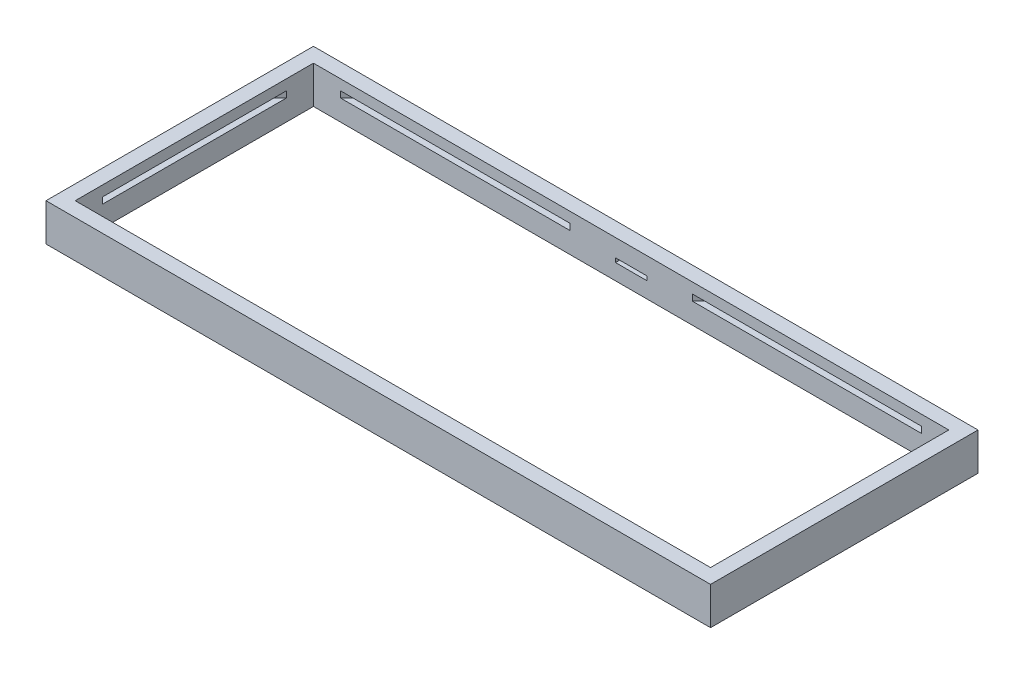
SolidWorks part; units mm, degrees
ref_plane "Front Plane" through (0, 0, 0) normal (0, 0, 1) x (1, 0, 0)
ref_plane "Top Plane" through (0, 0, 0) normal (0, 1, 0) x (1, 0, 0)
ref_plane "Right Plane" through (0, 0, 0) normal (1, 0, 0) x (0, 0, -1)
sketch "Sketch1" plane through (0, 0, 0) normal (0, 1, 0) x (1, 0, 0)
  line L0 (7, -7) -> (311.8, -7)
  line L1 (0, 0) -> (318.8, 0)
  line L2 (0, 0) -> (0, -128.3)
  line L3 (0, -128.3) -> (318.8, -128.3)
  line L4 (318.8, 0) -> (318.8, -128.3)
  line L5 (311.8, -7) -> (311.8, -121.3)
  line L6 (7, -121.3) -> (311.8, -121.3)
  line L7 (7, -7) -> (7, -121.3)
  dimension "D1" = 318.8
  dimension "D2" = 128.3
  dimension "D3" = 7
extrude "Boss-Extrude1" add sketch "Sketch1" along normal blind 8
sketch "Sketch2" plane through (0, 0, 0) normal (0, -1, 0) x (1, 0, 0)
  line L0 (7, 121.3) -> (311.8, 121.3) construction
  line L1 (20, 121.3) -> (130, 121.3)
  line L2 (20, 121.3) -> (20, 124.3)
  line L3 (20, 124.3) -> (130, 124.3)
  line L4 (130, 121.3) -> (130, 124.3)
  line L5 (159.4, 128.3) -> (159.4, 0)
  line L6 (0, 128.3) -> (318.8, 128.3) construction
  line L7 (318.8, 0) -> (0, 0) construction
  line L8 (0, 0) -> (0, 128.3) construction
  line L9 (0, 64.15) -> (318.8, 64.15)
  line L10 (318.8, 128.3) -> (318.8, 0) construction
  line L11 (20, 4) -> (130, 4)
  line L12 (130, 7) -> (130, 4)
  line L13 (20, 7) -> (130, 7)
  line L14 (20, 7) -> (20, 4)
  line L15 (7, 7) -> (7, 121.3) construction
  line L16 (7, 108.3) -> (4, 108.3)
  line L17 (7, 108.3) -> (7, 20)
  line L18 (7, 20) -> (4, 20)
  line L19 (4, 108.3) -> (4, 20)
  line L20 (298.8, 7) -> (298.8, 4)
  line L21 (298.8, 7) -> (188.8, 7)
  line L22 (188.8, 7) -> (188.8, 4)
  line L23 (298.8, 4) -> (188.8, 4)
  line L24 (311.8, 20) -> (314.8, 20)
  line L25 (314.8, 108.3) -> (314.8, 20)
  line L26 (311.8, 108.3) -> (314.8, 108.3)
  line L27 (311.8, 108.3) -> (311.8, 20)
  line L28 (298.8, 124.3) -> (188.8, 124.3)
  line L29 (188.8, 121.3) -> (188.8, 124.3)
  line L30 (298.8, 121.3) -> (188.8, 121.3)
  line L31 (298.8, 121.3) -> (298.8, 124.3)
  line M19 (7, 7) -> (7, 121.3)
  line M20 (7, 121.3) -> (311.8, 121.3)
  dimension "D1" = 110
  dimension "D2" = 3
  dimension "D3" = 20
  dimension "D4" = 20
  dimension "D5" = 20
  dimension "D6" = 3
extrude "Cut-Extrude1" cut sketch "Sketch2" against normal blind 3 contours L16 L19 L9 M19 | L4 L3 L2 M20 | L19 L18 L17 L16 | L28 L29 L30 L31 | L11 L12 L13 L14 | L23 L22 L21 L20 | L27 L24 L25 L26 region at (75, 0, 122.8) region at (5.5, 0, 86.225)
chamfer "Chamfer1" distance 3 angle 45 12 edges at (298.8, 1.5, 4) (314.8, 1.5, 20) (130, 1.5, 4) (188.8, 1.5, 4) (20, 1.5, 4) (4, 1.5, 20) (4, 1.5, 108.3) (314.8, 1.5, 108.3) (298.8, 1.5, 124.3) (188.8, 1.5, 124.3) (130, 1.5, 124.3) (20, 1.5, 124.3)
sketch "Sketch3" plane through (0, 0, 0) normal (0, -1, 0) x (1, 0, 0)
  line L1 (0, 128.3) -> (318.8, 128.3)
  line L2 (0, 128.3) -> (0, 0)
  line L3 (0, 0) -> (318.8, 0)
  line L4 (318.8, 128.3) -> (318.8, 0)
  line L5 (7, 121.3) -> (311.8, 121.3)
  line L6 (7, 121.3) -> (7, 7)
  line L7 (7, 7) -> (311.8, 7)
  line L8 (311.8, 121.3) -> (311.8, 7)
extrude "Boss-Extrude3" add sketch "Sketch3" along normal blind 10
sketch "Sketch4" plane through (0, 0, 0) normal (0, 0, -1) x (-1, 0, 0)
  line L0 (-318.8, 8) -> (0, 8) construction
  line L1 (-166.9, -0.4) -> (-151.9, -0.4)
  line L2 (-166.9, -0.4) -> (-166.9, -2.4)
  line L3 (-166.9, -2.4) -> (-151.9, -2.4)
  line L4 (-151.9, -0.4) -> (-151.9, -2.4)
  point P6 (-159.4, -0.4)
  point P7 (-159.4, 8)
  dimension "D1" = 15
  dimension "D2" = 2
  dimension "D3" = 8.4
  dimension "D4" = 0
extrude "Cut-Extrude3" cut sketch "Sketch4" against normal up to surface (7 mm away) up to face at (159.4, -1, 7)
